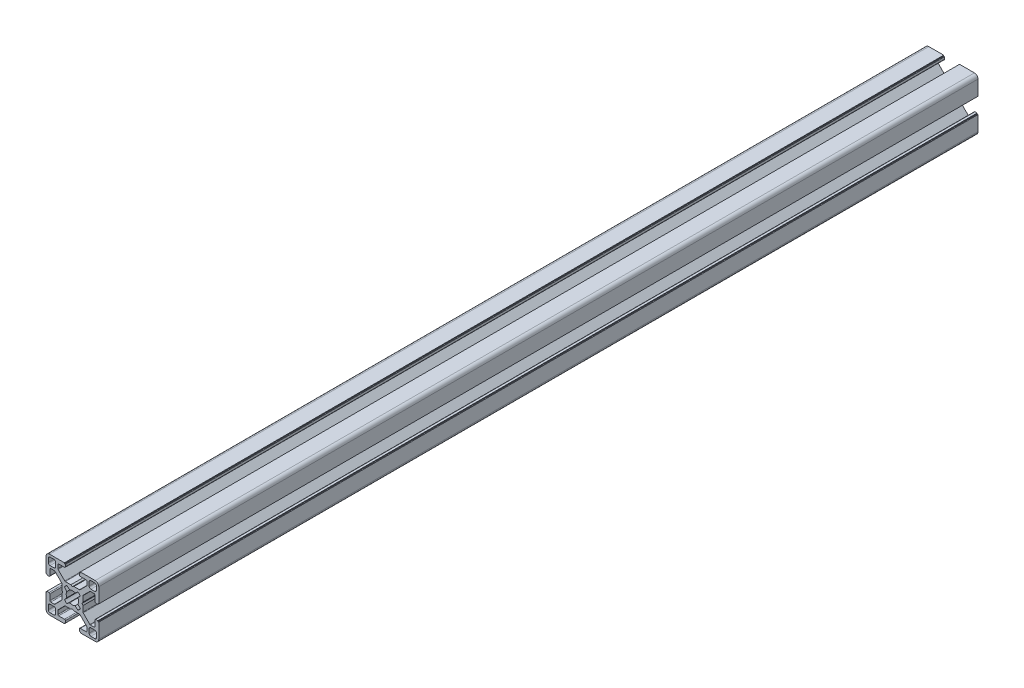
SolidWorks part; units mm, degrees
ref_plane "Front Plane" through (0, 0, 0) normal (0, 0, 1) x (1, 0, 0)
ref_plane "Top Plane" through (0, 0, 0) normal (0, 1, 0) x (1, 0, 0)
ref_plane "Right Plane" through (0, 0, 0) normal (1, 0, 0) x (0, 0, -1)
sketch "Sketch1" plane through (0, 0, 0) normal (0, 0, 1) x (1, 0, 0)
  line L0 (-15, 0) -> (15, 0) construction
  line L1 (0, -15) -> (0, 15) construction
  line L2 (-4.5, 15) -> (4.5, 15) construction
  line L3 (-4, -15) -> (4, -15) construction
  line L4 (-4.5, 15) -> (-4.5, 14.5)
  line L5 (-4.5, 14.5) -> (-4, 14.5)
  line L6 (-4, 14.5) -> (-4, 13.29)
  line L7 (-4.5, 12.79) -> (-7.7675, 12.79)
  line L8 (-8.2675, 12.29) -> (-8.2675, 10.2707)
  line L9 (-8.1211, 9.9171) -> (-4.3504, 6.1464)
  line L10 (-3.9968, 6) -> (0, 6)
  line L11 (0, 0) -> (-15, 15) construction
  line L12 (-4.5, 15) -> (-12.968, 15)
  line L14 (-12.705, 9.5135) -> (-10.5135, 9.5135)
  line L15 (-13.705, 10.5135) -> (-13.705, 12.705)
  line L16 (-12.705, 13.705) -> (-10.5135, 13.705)
  line L17 (-9.5135, 10.5135) -> (-9.5135, 12.705)
  line L18 (-13.705, 9.5135) -> (-9.5135, 13.705) construction
  line L19 (-13.705, 13.705) -> (-9.5135, 9.5135) construction
  line L20 (-3.1568, 4.5038) -> (-1.5303, 3.1477) construction
  line L21 (-4.5038, 3.1568) -> (-3.1477, 1.5303) construction
  line L22 (-6, 3.9968) -> (-6, 0)
  line L23 (-9.9171, 8.1211) -> (-6.1464, 4.3504)
  line L24 (-15, 4.5) -> (-15, 12.968)
  line L25 (-12.29, 8.2675) -> (-10.2707, 8.2675)
  line L26 (-12.79, 4.5) -> (-12.79, 7.7675)
  line L27 (-14.5, 4) -> (-13.29, 4)
  line L28 (-14.5, 4.5) -> (-14.5, 4)
  line L29 (-15, 4.5) -> (-14.5, 4.5)
  circle A0 centre (0, 0) radius 3.5
  arc A1 (-12.968, 15) -> (-15, 12.968) centre (-12.968, 12.968) ccw
  circle A2 centre (0, 0) radius 5.5 construction
  arc A3 (-10.5135, 9.5135) -> (-9.5135, 10.5135) centre (-10.5135, 10.5135) ccw
  arc A4 (-13.705, 12.705) -> (-12.705, 13.705) centre (-12.705, 12.705) cw
  arc A5 (-10.5135, 13.705) -> (-9.5135, 12.705) centre (-10.5135, 12.705) cw
  arc A6 (-12.705, 9.5135) -> (-13.705, 10.5135) centre (-12.705, 10.5135) cw
  arc A7 (-12.79, 4.5) -> (-13.29, 4) centre (-13.29, 4.5) cw
  arc A8 (-12.29, 8.2675) -> (-12.79, 7.7675) centre (-12.29, 7.7675) ccw
  arc A9 (-9.9171, 8.1211) -> (-10.2707, 8.2675) centre (-10.2707, 7.7675) ccw
  arc A10 (-6, 3.9968) -> (-6.1464, 4.3504) centre (-6.5, 3.9968) ccw
  arc A11 (-4.3504, 6.1464) -> (-3.9968, 6) centre (-3.9968, 6.5) ccw
  arc A12 (-4, 13.29) -> (-4.5, 12.79) centre (-4.5, 13.29) cw
  arc A13 (-7.7675, 12.79) -> (-8.2675, 12.29) centre (-7.7675, 12.29) ccw
  arc A14 (-8.2675, 10.2707) -> (-8.1211, 9.9171) centre (-7.7675, 10.2707) ccw
  point P4 (0, 0)
  point P8 (0, 0)
  point P13 (0, 15)
  point P15 (0, -15)
  point P16 (0, 6)
  point P23 (-11.6092, 11.6093)
  point P26 (0, 6)
  point P62 (-12.79, 4)
  point P65 (-12.79, 8.2675)
  point P68 (-10.0636, 8.2675)
  point P71 (-6, 4.2039)
  point P74 (-4.2039, 6)
  point P77 (-4, 12.79)
  point P80 (-8.2675, 12.79)
  point P83 (-8.2675, 10.0636)
  dimension "Center Hole Diameter" = 7
  dimension "D11" = 2.032
  dimension "D9" = 11
  dimension "D13" = 1
  dimension "D14" = 0.5
  dimension "Rail Height" = 30
  dimension "Rail Width" = 30
  dimension "T-Slot Width" = 8
  dimension "T-Slot Depth" = 9
  dimension "D1" = 9
  dimension "D2" = 45
  dimension "D3" = 8
  dimension "D4" = 2.21
  dimension "D5" = 16.535
  dimension "D7" = 2.54
  dimension "D6" = 1.295
  dimension "D8" = 1.246
  dimension "D10" = 10.36
  dimension "D12" = 1.905
sketch "Sketch2" plane through (0, 0, 0) normal (1, 0, 0) x (0, 0, -1)
  line L0 (-76.2, 0) -> (76.2, 0) construction
  line L2 (0, -15) -> (0, 15) construction
  line L3 (0, -15) -> (0, 15) construction
  line L4 (-76.2, -15) -> (-76.2, 15) construction
  line L5 (76.2, -15) -> (76.2, 15) construction
  point P0 (-38.7, 0)
  point P3 (0, 0)
  point P4 (38.7, 0)
  point P12 (-76.2, 0)
  point P14 (76.2, 0)
  dimension "Length" = 152.4
  dimension "D1" = 37.5
sketch "Sketch3" plane through (0, 0, 0) normal (0, 0, 1) x (1, 0, 0)
  line L0 (-4.5038, 3.1568) -> (-3.1477, 1.5303)
  line L1 (0, 3.5) -> (0, 5.5)
  line L2 (-5.5, 0) -> (-3.5, 0)
  line L7 (-6, 3.9968) -> (-6, 0) construction
  line L31 (-9.9171, 8.1211) -> (-6.1464, 4.3504) construction
  line L117 (-12.29, 8.2675) -> (-10.2707, 8.2675) construction
  line L118 (-12.79, 4.5) -> (-12.79, 7.7675) construction
  line L157 (-12.705, 9.5135) -> (-10.5135, 9.5135)
  line L158 (-9.5135, 10.5135) -> (-9.5135, 12.705)
  line L163 (-10.5135, 13.705) -> (-12.705, 13.705)
  line L164 (-13.705, 12.705) -> (-13.705, 10.5135)
  line L165 (-12.705, 9.5135) -> (-10.5135, 9.5135)
  line L166 (-9.5135, 10.5135) -> (-9.5135, 12.705)
  line L167 (-10.5135, 13.705) -> (-12.705, 13.705)
  line L168 (-13.705, 12.705) -> (-13.705, 10.5135)
  line L169 (-14.5, 4) -> (-13.29, 4) construction
  line L170 (-14.5, 4.5) -> (-14.5, 4) construction
  line L171 (-15, 4.5) -> (-14.5, 4.5) construction
  line L172 (-15, 4.5) -> (-15, 12.968) construction
  line L173 (-4.5, 15) -> (-12.968, 15) construction
  line L174 (-4.5, 15) -> (-4.5, 14.5) construction
  line L175 (-4.5, 14.5) -> (-4, 14.5) construction
  line L176 (-4, 14.5) -> (-4, 13.29) construction
  line L177 (-4.5, 12.79) -> (-7.7675, 12.79) construction
  line L178 (-8.2675, 12.29) -> (-8.2675, 10.2707) construction
  line L179 (-8.1211, 9.9171) -> (-4.3504, 6.1464) construction
  line L180 (-3.9968, 6) -> (0, 6) construction
  line L181 (-6, 3.9968) -> (-6, 0.866)
  line L182 (-9.9171, 8.1211) -> (-6.1464, 4.3504)
  line L183 (-12.29, 8.2675) -> (-10.2707, 8.2675)
  line L184 (-12.79, 4.5) -> (-12.79, 7.7675)
  line L185 (-14.5, 4) -> (-13.29, 4)
  line L186 (-14.5, 4.5) -> (-14.5, 4)
  line L187 (-15, 4.5) -> (-14.5, 4.5)
  line L188 (-15, 4.5) -> (-15, 12.968)
  line L189 (-4.5, 15) -> (-12.968, 15)
  line L190 (-4.5, 15) -> (-4.5, 14.5)
  line L191 (-4.5, 14.5) -> (-4, 14.5)
  line L192 (-4, 14.5) -> (-4, 13.29)
  line L193 (-4.5, 12.79) -> (-7.7675, 12.79)
  line L194 (-8.2675, 12.29) -> (-8.2675, 10.2707)
  line L195 (-8.1211, 9.9171) -> (-4.3504, 6.1464)
  line L196 (-3.9968, 6) -> (-0.866, 6)
  line L197 (-0.866, 6) -> (0, 5.5)
  line L198 (0, -15) -> (0, 15) construction
  line L199 (0, 0) -> (-15, 15) construction
  line L200 (0, 0) -> (-15, 15) construction
  line L201 (-3.1568, 4.5038) -> (-1.5303, 3.1477) construction
  line L202 (-3.1568, 4.5038) -> (-1.5303, 3.1477)
  line L203 (-6, 0.866) -> (-5.5, 0)
  line L204 (-15, 0) -> (15, 0) construction
  line L205 (-15, 0) -> (15, 0) construction
  line L206 (0, -15) -> (0, 15) construction
  arc A0 (-3.5, 0) -> (-3.1477, 1.5303) centre (0, 0) cw
  arc A10 (-6, 3.9968) -> (-6.1464, 4.3504) centre (-6.5, 3.9968) ccw construction
  circle A16 centre (0, 0) radius 3.5
  arc A18 (0, 3.5) -> (-1.5303, 3.1477) centre (0, 0) ccw
  arc A20 (-9.9171, 8.1211) -> (-10.2707, 8.2675) centre (-10.2707, 7.7675) ccw construction
  arc A22 (-12.29, 8.2675) -> (-12.79, 7.7675) centre (-12.29, 7.7675) ccw construction
  arc A28 (-13.29, 4) -> (-12.79, 4.5) centre (-13.29, 4.5) ccw construction
  arc A29 (-10.5135, 9.5135) -> (-9.5135, 10.5135) centre (-10.5135, 10.5135) ccw
  arc A30 (-9.5135, 12.705) -> (-10.5135, 13.705) centre (-10.5135, 12.705) ccw
  arc A31 (-12.705, 13.705) -> (-13.705, 12.705) centre (-12.705, 12.705) ccw
  arc A32 (-13.705, 10.5135) -> (-12.705, 9.5135) centre (-12.705, 10.5135) ccw
  arc A33 (-10.5135, 9.5135) -> (-9.5135, 10.5135) centre (-10.5135, 10.5135) ccw
  arc A34 (-9.5135, 12.705) -> (-10.5135, 13.705) centre (-10.5135, 12.705) ccw
  arc A35 (-12.705, 13.705) -> (-13.705, 12.705) centre (-12.705, 12.705) ccw
  arc A36 (-13.705, 10.5135) -> (-12.705, 9.5135) centre (-12.705, 10.5135) ccw
  arc A37 (-12.968, 15) -> (-15, 12.968) centre (-12.968, 12.968) ccw construction
  arc A38 (-4.5, 12.79) -> (-4, 13.29) centre (-4.5, 13.29) ccw construction
  arc A39 (-7.7675, 12.79) -> (-8.2675, 12.29) centre (-7.7675, 12.29) ccw construction
  arc A40 (-8.2675, 10.2707) -> (-8.1211, 9.9171) centre (-7.7675, 10.2707) ccw construction
  arc A41 (-4.3504, 6.1464) -> (-3.9968, 6) centre (-3.9968, 6.5) ccw construction
  arc A42 (-6, 3.9968) -> (-6.1464, 4.3504) centre (-6.5, 3.9968) ccw
  arc A43 (-9.9171, 8.1211) -> (-10.2707, 8.2675) centre (-10.2707, 7.7675) ccw
  arc A44 (-12.29, 8.2675) -> (-12.79, 7.7675) centre (-12.29, 7.7675) ccw
  arc A45 (-13.29, 4) -> (-12.79, 4.5) centre (-13.29, 4.5) ccw
  arc A46 (-12.968, 15) -> (-15, 12.968) centre (-12.968, 12.968) ccw
  arc A47 (-4.5, 12.79) -> (-4, 13.29) centre (-4.5, 13.29) ccw
  arc A48 (-7.7675, 12.79) -> (-8.2675, 12.29) centre (-7.7675, 12.29) ccw
  arc A49 (-8.2675, 10.2707) -> (-8.1211, 9.9171) centre (-7.7675, 10.2707) ccw
  arc A50 (-4.3504, 6.1464) -> (-3.9968, 6) centre (-3.9968, 6.5) ccw
  circle A51 centre (0, 0) radius 5.5 construction
  arc A52 (-3.1568, 4.5038) -> (-4.5038, 3.1568) centre (0, 0) ccw
  dimension "D3" = 60
  dimension "D4" = 60
  dimension "D1" = 0
  dimension "D2" = 0
extrude "Boss-Extrude1" add sketch "Sketch3" along normal mid plane 500
pattern_circular "CirPattern1" count 4 over 360 about axis through (0, 0, 76.2) along (0, 0, -1) of "Boss-Extrude1"
ref_plane "Contact Plane1" through (15, 0, 0) normal (1, 0, 0) x (0, 0, -1)
ref_plane "Contact Plane2" through (0, -15, 0) normal (0, 1, 0) x (1, 0, 0)
ref_plane "Contact Plane3" through (-15, 0, 0) normal (1, 0, 0) x (0, 0, -1)
ref_plane "Contact Plane4" through (0, 15, 0) normal (0, 1, 0) x (1, 0, 0)
equation "\"D1@Sketch2\" = \"Rail Height@Sketch1\" * 1.25"
equation "\"D1@Sketch1\"=\"T-Slot Width@Sketch1\"+1mm"
equation "\"D3@Sketch1\"=\"T-Slot Width@Sketch1\""
equation "\"D1@Boss-Extrude1\"=\"Length\""
equation "\"Length\"= 500"
